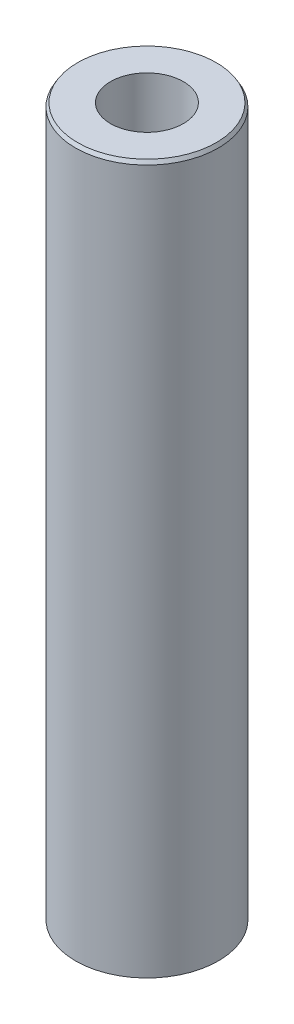
SolidWorks part; units mm, degrees
ref_plane "Front Plane" through (0, 0, 0) normal (0, 0, 1) x (1, 0, 0)
ref_plane "Top Plane" through (0, 0, 0) normal (0, 1, 0) x (1, 0, 0)
ref_plane "Right Plane" through (0, 0, 0) normal (1, 0, 0) x (0, 0, -1)
sketch "Sketch1" plane through (0, 0, 0) normal (0, 1, 0) x (1, 0, 0)
  circle A0 centre (0, 0) radius 47.5
  dimension "SHAFT_OD" = 95
extrude "Boss-Extrude1" add sketch "Sketch1" along normal blind 471.9756
sketch "Sketch2" plane through (0, 0, 0) normal (0, 1, 0) x (1, 0, 0)
  circle A0 centre (0, 0) radius 24.2295
  dimension "BORE_D" = 48.459
extrude "Cut-Extrude1" cut sketch "Sketch2" along normal through all
chamfer "Chamfer1" distance 2.4124 angle 30 2 edges at (0, 471.9756, 47.5) (0, 0, 47.5) first distance on face at (0, 471.9756, 47.5) first distance on face at (0, 0, 24.2295)
